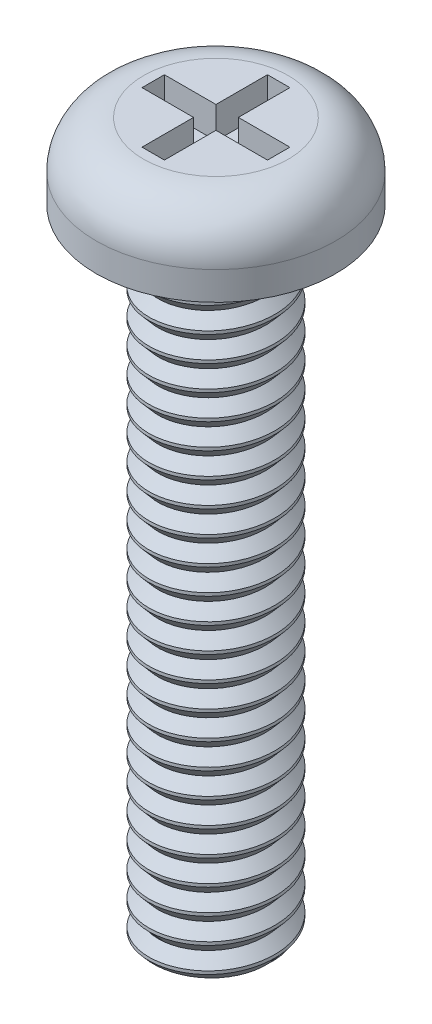
SolidWorks part; units mm, degrees
material "Plain Carbon Steel"
ref_plane "Front Plane" through (0, 0, 0) normal (0, 0, 1) x (1, 0, 0)
ref_plane "Top Plane" through (0, 0, 0) normal (0, 1, 0) x (1, 0, 0)
ref_plane "Right Plane" through (0, 0, 0) normal (1, 0, 0) x (0, 0, -1)
sketch "Sketch1" plane through (0, 0, 0) normal (0, 1, 0) x (1, 0, 0)
  circle A0 centre (0, 0) radius 1.9
  dimension "D1" = 3.8
extrude "Boss-Extrude1" add sketch "Sketch1" along normal blind 1.2 contours A0
sketch "Sketch2" plane through (0, 1.2, 0) normal (0, 1, 0) x (1, 0, 0)
  line L0 (0, -0.9961) -> (0, 0.9961) construction
  line L1 (0.9961, 0) -> (-0.9961, 0) construction
  line L2 (-0.9961, 0.1778) -> (-0.9961, -0.1778)
  line L7 (-0.9961, -0.1778) -> (-0.1778, -0.1778)
  line L8 (-0.1778, -0.1778) -> (-0.1778, -0.9961)
  line L9 (-0.1778, -0.9961) -> (0.1778, -0.9961)
  line L10 (0.1778, -0.9961) -> (0.1778, -0.1778)
  line L11 (0.1778, -0.1778) -> (0.9961, -0.1778)
  line L12 (0.9961, -0.1778) -> (0.9961, 0.1778)
  line L13 (0.9961, 0.1778) -> (0.1778, 0.1778)
  line L14 (0.1778, 0.1778) -> (0.1778, 0.9961)
  line L15 (0.1778, 0.9961) -> (-0.1778, 0.9961)
  line L16 (-0.1778, 0.9961) -> (-0.1778, 0.1778)
  line L17 (-0.1778, 0.1778) -> (-0.9961, 0.1778)
extrude "Cut-Extrude1" cut sketch "Sketch2" against normal blind 0.5
fillet "Fillet1" radius 0.75 1 edges at (0, 1.2, 1.9)
sketch "Sketch3" plane through (0, 0, 0) normal (0, 1, 0) x (1, 0, 0)
  circle A0 centre (0, 0) radius 1
  dimension "D1" = 2
extrude "Boss-Extrude2" add sketch "Sketch3" against normal blind 10
sketch "Sketch4" plane through (0, 0, 0) normal (0, 0, 1) x (1, 0, 0)
  line L0 (0, 0) -> (0, -10) construction
  line L1 (-1, -10) -> (1, -10) construction
  line L2 (0, -10) -> (0.85, -10) construction
  line L3 (0.85, -10) -> (1, -9.825)
  line L4 (1, -10) -> (1, 0) construction
  line L5 (1, -9.825) -> (1, -10.175)
  line L6 (1, -10.175) -> (0.85, -10)
  point P5 (1, -10)
  dimension "D1" = 0.35
  dimension "D2" = 0.15
sketch "Sketch5" plane through (0, -10, 0) normal (0, -1, 0) x (1, 0, 0)
  circle A0 centre (0, 0) radius 1
  circle A1 centre (0, 0) radius 1 construction
curve "Helix/Spiral1" pitch 0.4 height 10 radius 1 centre (0, -10, 0) axis (0, 1, 0) start towards (1, 0, 0)
sweep "Cut-Sweep1" cut profiles "Sketch4" path "Helix/Spiral1" align with end faces yes
